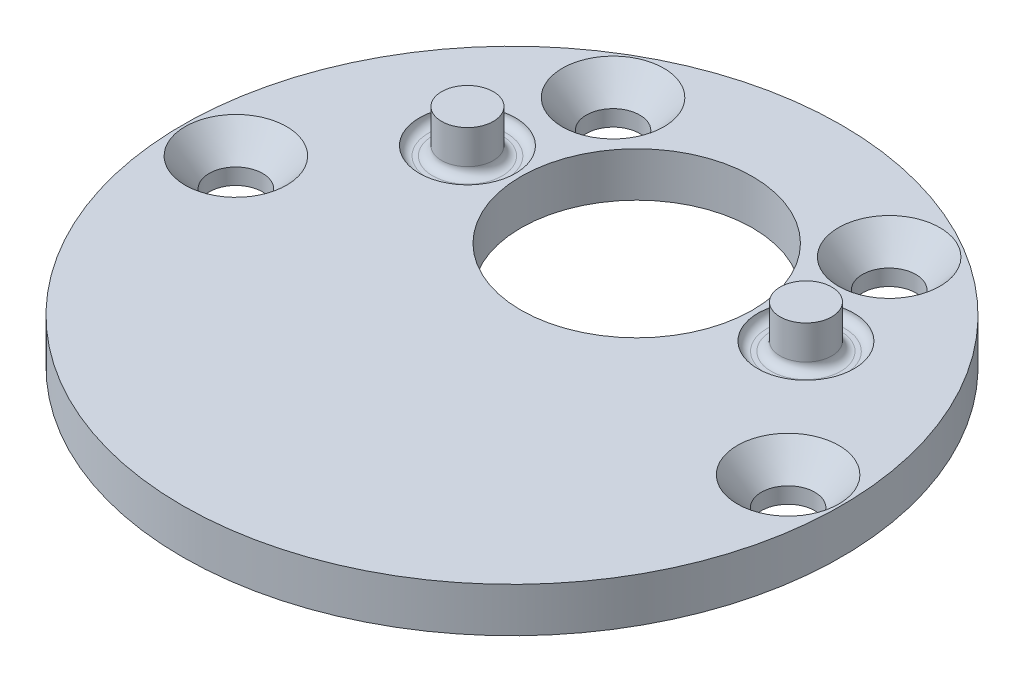
SolidWorks part; units mm, degrees
ref_plane "Front Plane" through (0, 0, 0) normal (0, 0, 1) x (1, 0, 0)
ref_plane "Top Plane" through (0, 0, 0) normal (0, 1, 0) x (1, 0, 0)
ref_plane "Right Plane" through (0, 0, 0) normal (1, 0, 0) x (0, 0, -1)
sketch "Sketch1" plane through (0, 0, 0) normal (0, 1, 0) x (1, 0, 0)
  line L4 (0, 0) -> (15.8817, 0) construction
  line L5 (0, 0) -> (0, 17.0912) construction
  line L6 (-7.75, 13.4234) -> (0, 0) construction
  line L7 (0, 0) -> (7.75, 13.4234) construction
  circle A0 centre (0, 0) radius 15.5 construction
  circle A1 centre (-7.75, 13.4234) radius 1.5
  circle A3 centre (-15.5, 0) radius 1.5
  circle A4 centre (7.75, 13.4234) radius 1.5
  circle A5 centre (15.5, 0) radius 1.5
  circle A6 centre (0, 0) radius 18.5
  dimension "D1" = 31
  dimension "D2" = 3
  dimension "D4" = 37
  dimension "D3" = 60
extrude "Boss-Extrude1" add sketch "Sketch1" along normal blind 2.5
sketch "Sketch2" plane through (0, 2.5, 0) normal (0, 1, 0) x (1, 0, 0)
  line L0 (0, 0) -> (0, 16.6144) construction
  line L1 (0, 0) -> (25.2906, 0) construction
  line L2 (-9.5, 7) -> (9.5, 7) construction
  circle A0 centre (-9.5, 7) radius 1.45
  circle A1 centre (9.5, 7) radius 1.45
  point P8 (0, 8.3072)
  point P11 (0, 7)
  dimension "D3" = 2.9
  dimension "D1" = 7
  dimension "D2" = 19
extrude "Boss-Extrude2" add sketch "Sketch2" along normal blind 1.9 and the other way blind 1
sketch "Sketch6" plane through (0, 2.5, 0) normal (0, 1, 0) x (1, 0, 0)
  line L0 (9.5, 7) -> (-9.5, 7) construction
  line L1 (0, 0) -> (0, 7) construction
  circle A0 centre (-9.5, 7) radius 2.7
  circle A1 centre (9.5, 7) radius 2.7
  circle A2 centre (-9.5, 7) radius 1.45 construction
  circle A3 centre (9.5, 7) radius 1.45
  circle A4 centre (-9.5, 7) radius 1.45
  circle A5 centre (9.5, 7) radius 1.45 construction
  dimension "D1" = 1.25
extrude "Cut-Extrude3" cut sketch "Sketch6" against normal blind 0.5
sketch "Sketch4" plane through (0, 2.5, 0) normal (0, 1, 0) x (1, 0, 0)
  line L0 (9.5, 7) -> (-9.5, 7) construction
  circle A0 centre (0, 7) radius 6.5
  dimension "D1" = 13
extrude "Cut-Extrude1" cut sketch "Sketch4" against normal through all
chamfer "Chamfer1" distance 1.35 distance2 1.6 4 edges at (-15.5, 2.5, 1.5) (15.5, 2.5, 1.5) (7.75, 2.5, -11.9234) (-7.75, 2.5, -11.9234) first distance on face at (0, 2.5, -0.5)
fillet "Fillet1" radius 0.5 4 edges at (9.5, 2, -4.3) (9.5, 2, -5.55) (-9.5, 2, -4.3) (-9.5, 2, -5.55)
